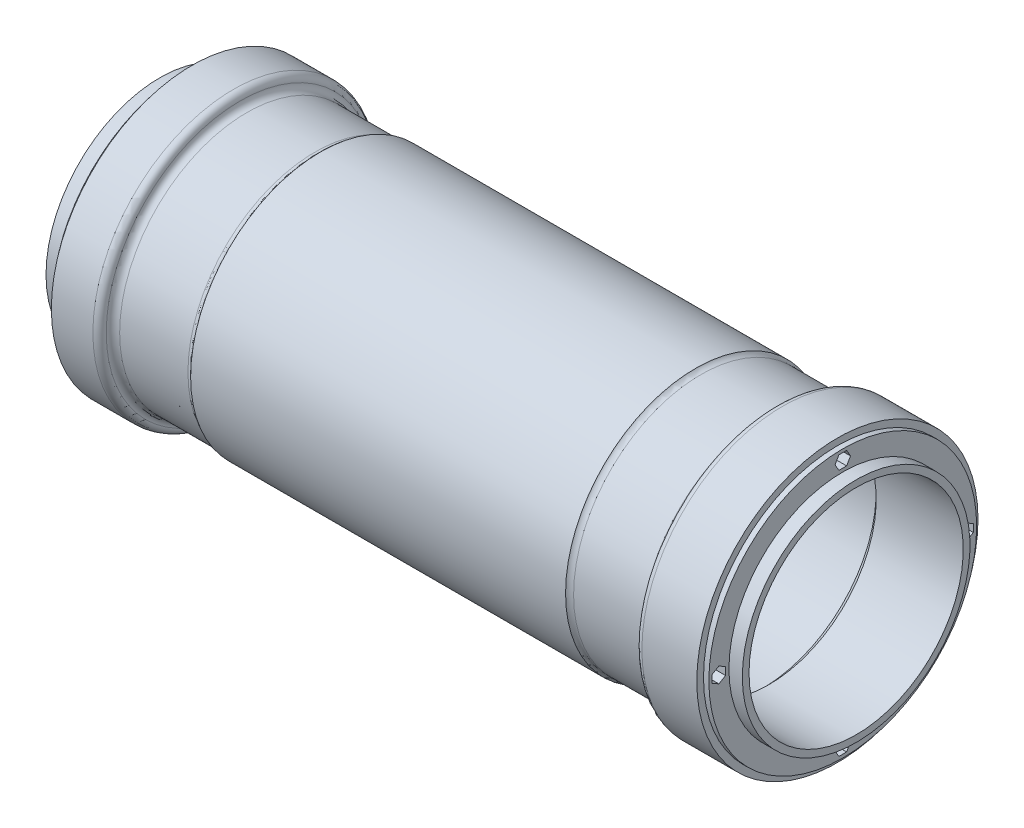
SolidWorks part; units mm, degrees
ref_plane "Front Plane" through (0, 0, 0) normal (0, 0, 1) x (1, 0, 0)
ref_plane "Top Plane" through (0, 0, 0) normal (0, 1, 0) x (1, 0, 0)
ref_plane "Right Plane" through (0, 0, 0) normal (1, 0, 0) x (0, 0, -1)
sketch "Sketch2" plane through (0, 0, 0) normal (0, 1, 0) x (1, 0, 0)
  line L0 (-130, 0) -> (130, 0) construction
  line L1 (100.5, -42.5) -> (-99.5, -42.5)
  line L2 (-129.5, -40) -> (-119.5, -40)
  line L3 (-119.5, -40) -> (-119.5, -37.5)
  line L4 (-119.5, -37.5) -> (-117.5, -37.5)
  line L5 (-117.5, -37.5) -> (-117.5, -40)
  line L9 (-117.5, -52.5) -> (-117.5, -50)
  line L10 (-117.5, -50) -> (-119.5, -50)
  line L11 (-119.5, -50) -> (-119.5, -42.5)
  line L12 (-119.5, -42.5) -> (-129.5, -42.5)
  line L13 (-129.5, -42.5) -> (-129.5, -40)
  line L34 (-117.5, -52.5) -> (-99.5, -52.5)
  line L43 (123.5, -52.5) -> (123.5, -50)
  line L44 (123.5, -50) -> (125.5, -50)
  line L45 (125.5, -50) -> (125.5, -42.5)
  line L46 (125.5, -42.5) -> (130.5, -42.5)
  line L47 (130.5, -42.5) -> (130.5, -40)
  line L48 (130.5, -40) -> (100.5, -40)
  line L49 (100.5, -40) -> (100.5, -42.5)
  line L59 (-99.5, -42.5) -> (-99.5, -40)
  line L60 (-99.5, -40) -> (-117.5, -40)
  line L61 (70.5, -48.5) -> (70.5, -47.5)
  line L62 (70.5, -47.5) -> (100.5, -47.5)
  line L63 (100.5, -47.5) -> (100.5, -52.5)
  line L64 (100.5, -52.5) -> (123.5, -52.5)
  line L65 (-69.5, -48.5) -> (-69.5, -47.5)
  line L66 (-69.5, -47.5) -> (-99.5, -47.5)
  line L67 (-99.5, -47.5) -> (-99.5, -52.5)
  line L74 (-69.5, -48.5) -> (70.5, -48.5)
  point P4 (0, 0)
  dimension "D3" = 10
  dimension "D4" = 2.5
  dimension "D5" = 2
  dimension "D6" = 2.5
  dimension "D7" = 18
  dimension "D8" = 2.5
  dimension "D9" = 10
  dimension "D10" = 7.5
  dimension "D11" = 2
  dimension "D12" = 2.5
  dimension "D19" = 2.5
  dimension "D20" = 30
  dimension "D21" = 5
  dimension "D22" = 200
  dimension "D23" = 2
  dimension "D24" = 2.5
  dimension "D25" = 7.5
  dimension "D26" = 2.5
  dimension "D27" = 5
  dimension "D28" = 30
  dimension "D30" = 23
  dimension "D34" = 1
  dimension "D35" = 18
  dimension "D37" = 5
  dimension "D38" = 30
  dimension "D39" = 5
revolve "Revolve1" add sketch "Sketch2" angle 360 about L0
chamfer "Chamfer5" distance 5 angle 45 3 edges at (-99.5, 0, 40) (-117.5, 0, 40) (100.5, 0, 42.5)
fillet "Fillet1" radius 2.5 4 edges at (-69.5, 0, 47.5) (70.5, 0, 47.5) (100.5, 0, 47.5) (-99.5, 0, 47.5)
fillet "Fillet2" radius 2.5 2 edges at (-99.5, 0, 52.5) (100.5, 0, 52.5)
sketch "Sketch3" plane through (-119.5, 0, 0) normal (-1, 0, 0) x (0, 0, 1)
  line L1 (2.8868, 46.25) -> (1.4434, 48.75)
  line L2 (1.4434, 48.75) -> (-1.4434, 48.75)
  line L3 (-1.4434, 48.75) -> (-2.8868, 46.25)
  line L4 (-2.8868, 46.25) -> (-1.4434, 43.75)
  line L5 (-1.4434, 43.75) -> (1.4434, 43.75)
  line L6 (1.4434, 43.75) -> (2.8868, 46.25)
  line L7 (46.25, -2.8868) -> (48.75, -1.4434)
  line L8 (48.75, -1.4434) -> (48.75, 1.4434)
  line L9 (48.75, 1.4434) -> (46.25, 2.8868)
  line L10 (46.25, 2.8868) -> (43.75, 1.4434)
  line L11 (43.75, 1.4434) -> (43.75, -1.4434)
  line L12 (43.75, -1.4434) -> (46.25, -2.8868)
  line L13 (-46.25, -2.8868) -> (-43.75, -1.4434)
  line L14 (-43.75, -1.4434) -> (-43.75, 1.4434)
  line L15 (-43.75, 1.4434) -> (-46.25, 2.8868)
  line L16 (-46.25, 2.8868) -> (-48.75, 1.4434)
  line L17 (-48.75, 1.4434) -> (-48.75, -1.4434)
  line L18 (-48.75, -1.4434) -> (-46.25, -2.8868)
  line L19 (2.8868, -46.25) -> (1.4434, -43.75)
  line L20 (1.4434, -43.75) -> (-1.4434, -43.75)
  line L21 (-1.4434, -43.75) -> (-2.8868, -46.25)
  line L22 (-2.8868, -46.25) -> (-1.4434, -48.75)
  line L23 (-1.4434, -48.75) -> (1.4434, -48.75)
  line L24 (1.4434, -48.75) -> (2.8868, -46.25)
  circle A0 centre (0, 46.25) radius 2.5 construction
  circle A1 centre (46.25, 0) radius 2.5 construction
  circle A2 centre (-46.25, 0) radius 2.5 construction
  circle A3 centre (0, -46.25) radius 2.5 construction
  point P1 (0, 48.75)
  dimension "D1" = 5
  dimension "D2" = 46.25
  dimension "D3" = 5
  dimension "D4" = 46.25
  dimension "D5" = 46.25
  dimension "D6" = 5
  dimension "D7" = 5
  dimension "D8" = 46.25
extrude "Cut-Extrude1" cut sketch "Sketch3" against normal blind 10
sketch "Sketch5" plane through (125.5, 0, 0) normal (1, 0, 0) x (0, 0, -1)
  line L1 (2.8868, 46.25) -> (1.4434, 48.75)
  line L2 (1.4434, 48.75) -> (-1.4434, 48.75)
  line L3 (-1.4434, 48.75) -> (-2.8868, 46.25)
  line L4 (-2.8868, 46.25) -> (-1.4434, 43.75)
  line L5 (-1.4434, 43.75) -> (1.4434, 43.75)
  line L6 (1.4434, 43.75) -> (2.8868, 46.25)
  line L7 (46.25, -2.8868) -> (48.75, -1.4434)
  line L8 (48.75, -1.4434) -> (48.75, 1.4434)
  line L9 (48.75, 1.4434) -> (46.25, 2.8868)
  line L10 (46.25, 2.8868) -> (43.75, 1.4434)
  line L11 (43.75, 1.4434) -> (43.75, -1.4434)
  line L12 (43.75, -1.4434) -> (46.25, -2.8868)
  line L13 (2.8868, -46.25) -> (1.4434, -43.75)
  line L14 (1.4434, -43.75) -> (-1.4434, -43.75)
  line L15 (-1.4434, -43.75) -> (-2.8868, -46.25)
  line L16 (-2.8868, -46.25) -> (-1.4434, -48.75)
  line L17 (-1.4434, -48.75) -> (1.4434, -48.75)
  line L18 (1.4434, -48.75) -> (2.8868, -46.25)
  line L19 (-46.25, -2.8868) -> (-43.75, -1.4434)
  line L20 (-43.75, -1.4434) -> (-43.75, 1.4434)
  line L21 (-43.75, 1.4434) -> (-46.25, 2.8868)
  line L22 (-46.25, 2.8868) -> (-48.75, 1.4434)
  line L23 (-48.75, 1.4434) -> (-48.75, -1.4434)
  line L24 (-48.75, -1.4434) -> (-46.25, -2.8868)
  circle A0 centre (0, 46.25) radius 2.5 construction
  circle A1 centre (46.25, 0) radius 2.5 construction
  circle A2 centre (0, -46.25) radius 2.5 construction
  circle A3 centre (-46.25, 0) radius 2.5 construction
  dimension "D1" = 5
  dimension "D2" = 5
  dimension "D3" = 5
  dimension "D4" = 5
  dimension "D5" = 46.25
  dimension "D6" = 46.25
  dimension "D7" = 46.25
  dimension "D8" = 46.25
extrude "Cut-Extrude2" cut sketch "Sketch5" against normal blind 10
